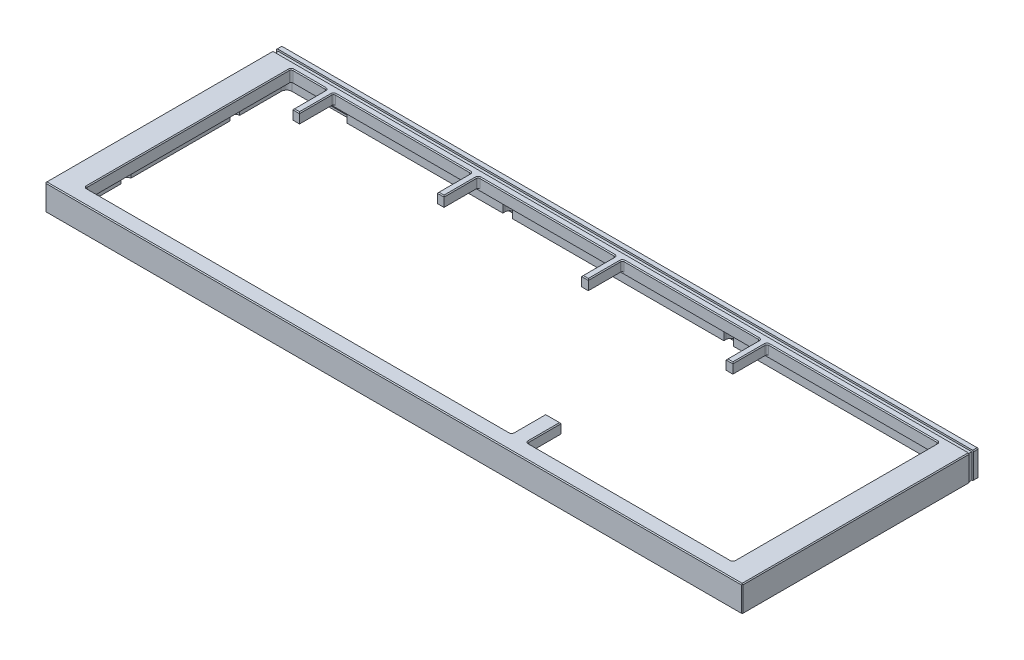
SolidWorks part; units mm, degrees
material "6061-T6 (SS)"
ref_plane "Front Plane" through (0, 0, 0) normal (0, 0, 1) x (1, 0, 0)
ref_plane "Top Plane" through (0, 0, 0) normal (0, 1, 0) x (1, 0, 0)
ref_plane "Right Plane" through (0, 0, 0) normal (1, 0, 0) x (0, 0, -1)
sketch "Sketch1" plane through (0, 0, 0) normal (0, 1, 0) x (1, 0, 0)
  line L1 (0, 0) -> (390.74, 0)
  line L2 (0, 0) -> (0, 132.7)
  line L3 (0, 132.7) -> (390.74, 132.7)
  line L4 (390.74, 0) -> (390.74, 132.7)
  line L5 (13.92, 124) -> (376.82, 124)
  line L6 (13.92, 124) -> (13.92, 8.7)
  line L7 (13.92, 8.7) -> (376.82, 8.7)
  line L8 (376.82, 124) -> (376.82, 8.7)
  point P9 (195.37, 124)
  point P10 (195.37, 132.7)
  point P11 (13.92, 66.35)
  point P12 (0, 66.35)
  dimension "D1" = 362.9
  dimension "D2" = 115.3
  dimension "D3" = 8.7
  dimension "D4" = 13.92
extrude "Main Body" add sketch "Sketch1" along normal blind 14.8
sketch "Sketch2" plane through (0, 0, 0) normal (0, -1, 0) x (1, 0, 0)
  line L0 (390.74, -132.7) -> (0, -132.7) construction
  line L1 (388.74, -130.7) -> (2, -130.7)
  line L2 (388.74, -130.7) -> (388.74, -2)
  line L3 (388.74, -2) -> (2, -2)
  line L4 (2, -130.7) -> (2, -2)
  line L5 (390.74, 0) -> (390.74, -132.7) construction
  point P4 (195.37, -130.7)
  point P7 (195.37, -132.7)
  point P8 (388.74, -66.35)
  point P11 (390.74, -66.35)
  dimension "D1" = 2
  dimension "D2" = 2
extrude "Alignment Guide" cut sketch "Sketch2" against normal blind 2 contours L2 L1 L4 L3
sketch "Sketch3" plane through (0, 14.8, 0) normal (0, 1, 0) x (1, 0, 0)
  line L0 (13.92, 8.7) -> (376.82, 8.7) construction
  line L1 (252.82, 27.8) -> (261.52, 27.8)
  line L2 (252.82, 27.8) -> (252.82, 8.7)
  line L3 (252.82, 8.7) -> (261.52, 8.7)
  line L4 (261.52, 27.8) -> (261.52, 8.7)
  line L5 (376.82, 8.7) -> (376.82, 124) construction
  line L6 (376.82, 124) -> (13.92, 124) construction
  line L7 (33.92, 124) -> (37.72, 124)
  line L8 (33.92, 124) -> (33.92, 104.9)
  line L9 (33.92, 104.9) -> (37.72, 104.9)
  line L10 (37.72, 124) -> (37.72, 104.9)
  line L11 (13.92, 124) -> (13.92, 8.7) construction
  line L12 (114.92, 124) -> (118.72, 124)
  line L13 (114.92, 124) -> (114.92, 104.9)
  line L14 (114.92, 104.9) -> (118.72, 104.9)
  line L15 (118.72, 124) -> (118.72, 104.9)
  line L16 (195.82, 124) -> (199.62, 124)
  line L17 (195.82, 124) -> (195.82, 104.9)
  line L18 (195.82, 104.9) -> (199.62, 104.9)
  line L19 (199.62, 124) -> (199.62, 104.9)
  line L20 (276.82, 124) -> (280.62, 124)
  line L21 (276.82, 124) -> (276.82, 104.9)
  line L22 (276.82, 104.9) -> (280.62, 104.9)
  line L23 (280.62, 124) -> (280.62, 104.9)
  point P8 (257.17, 8.7)
  dimension "D1" = 115.3
  dimension "D2" = 124
  dimension "D3" = 19.1
  dimension "D4" = 3.8
  dimension "D5" = 19.1
  dimension "D6" = 77.2
  dimension "D7" = 77.1
  dimension "D8" = 77.2
  dimension "D9" = 20
extrude "Blockers" add sketch "Sketch3" against normal blind 5.5
fillet "Fillet5" radius 1 14 edges at (280.62, 12.05, -124) (276.82, 12.05, -124) (195.82, 12.05, -124) (199.62, 12.05, -124) (118.72, 12.05, -124) (114.92, 12.05, -124) (33.92, 12.05, -124) (37.72, 12.05, -124) (13.92, 8.4, -124) (13.92, 8.4, -8.7) (252.82, 12.05, -8.7) (261.52, 12.05, -8.7) (376.82, 8.4, -8.7) (376.82, 8.4, -124)
sketch "Sketch4" plane through (0, 2, 0) normal (0, -1, 0) x (1, 0, 0)
  line L0 (0, 0) -> (390.74, 0) construction
  line L1 (381.27, -125.9) -> (9.47, -125.9)
  line L2 (381.27, -125.9) -> (381.27, -6.8)
  line L3 (381.27, -6.8) -> (9.47, -6.8)
  line L4 (9.47, -125.9) -> (9.47, -6.8)
  line L5 (390.74, 0) -> (390.74, -132.7) construction
  point P4 (195.37, -6.8)
  point P7 (195.37, 0)
  point P8 (381.27, -66.35)
  point P11 (390.74, -66.35)
  dimension "D1" = 119.1
  dimension "D2" = 371.8
extrude "PCB Cutout" cut sketch "Sketch4" against normal offset from surface (6.3 mm away) 6.5 up to face at (195.37, 14.8, -66.35)
fillet "Fillet4" radius 3 8 edges at (9.47, 5.15, -6.8) (9.47, 5.15, -125.9) (381.27, 5.15, -125.9) (381.27, 5.15, -6.8) (2, 1, -130.7) (2, 1, -2) (388.74, 1, -2) (388.74, 1, -130.7)
sketch "Sketch6" plane through (0, 2, 0) normal (0, -1, 0) x (1, 0, 0)
  line L0 (381.27, -9.8) -> (381.27, -122.9) construction
  line L1 (254.59, -127.1) -> (260.09, -127.1)
  line L2 (254.59, -127.1) -> (254.59, -125.9)
  line L3 (254.59, -125.9) -> (260.09, -125.9)
  line L4 (260.09, -127.1) -> (260.09, -125.9)
  line L5 (12.47, -125.9) -> (378.27, -125.9) construction
  line L11 (378.27, -6.8) -> (12.47, -6.8) construction
  line L16 (260.09, -6.8) -> (254.59, -6.8)
  line L17 (260.09, -6.8) -> (260.09, -4.8)
  line L18 (260.09, -4.8) -> (254.59, -4.8)
  line L19 (254.59, -6.8) -> (254.59, -4.8)
  line L21 (0, 0) -> (390.74, 0) construction
  line L24 (390.74, -66.35) -> (195.37, -66.35) construction
  line L25 (390.74, 0) -> (390.74, -132.7) construction
  line L26 (328.6755, -66.35) -> (328.6755, -130.7) construction
  line L27 (385.74, -130.7) -> (5, -130.7) construction
  line L28 (328.6755, -66.35) -> (328.6755, -8.7) construction
  line L29 (375.82, -8.7) -> (14.92, -8.7) construction
  line L55 (390.74, -132.7) -> (0, -132.7) construction
  line L56 (195.37, -132.7) -> (195.37, 0) construction
  line L57 (136.15, -6.8) -> (136.15, -4.8)
  line L58 (130.65, -4.8) -> (136.15, -4.8)
  line L59 (130.65, -6.8) -> (130.65, -4.8)
  line L60 (130.65, -6.8) -> (136.15, -6.8)
  line L61 (130.65, -127.1) -> (130.65, -125.9)
  line L62 (136.15, -125.9) -> (130.65, -125.9)
  line L63 (136.15, -127.1) -> (136.15, -125.9)
  line L64 (136.15, -127.1) -> (130.65, -127.1)
  circle A0 centre (381.07, -96.85) radius 2.75
  circle A1 centre (381.07, -35.85) radius 2.75
  circle A2 centre (257.34, -4.8) radius 2.75
  circle A3 centre (257.34, -127.1) radius 2.75
  circle A8 centre (133.4, -4.8) radius 2.75
  circle A9 centre (9.67, -35.85) radius 2.75
  circle A10 centre (9.67, -96.85) radius 2.75
  circle A11 centre (133.4, -127.1) radius 2.75
  point P25 (195.37, -66.35)
  point P32 (257.34, -125.9)
  point P33 (257.34, -6.8)
  line M17 (12.47, -6.8) -> (378.27, -6.8)
  line M18 (381.27, -9.8) -> (381.27, -122.9)
  line M19 (378.27, -125.9) -> (12.47, -125.9)
  line M20 (9.47, -122.9) -> (9.47, -9.8)
  dimension "D4" = 5.5
  dimension "D5" = 133.4
  dimension "D1" = 30.5
  dimension "D2" = 4.8
  dimension "D3" = 30.5
  dimension "D6" = 0.2
  dimension "D7" = 5.6
extrude "PlateTabs" cut sketch "Sketch6" against normal up to surface (6.3 mm away) contours A0 M18 | A1 M18 | A2 L19 M17 | L16 A2 L18 | A2 L17 M17 | L18 A2 | L1 A3 | L1 A3 L3 | A3 L2 M19 | A11 L64 | A11 L64 L62 | A10 M20 | A9 M20 | A8 L58 | A8 L60 L58 | A3 L4 M19 | A8 L59 M17 | L57 A8 M17 | A11 L63 M19 | L61 A11 M19 | A11 | L59 L58 L57 L60 | A3 region at (257.34, 2, -126.5102) region at (136.0681, 2, -126.1969) region at (257.34, 2, -128.2671) region at (254.6719, 2, -126.1969) region at (260.0081, 2, -126.1969) region at (133.4, 2, -126.5102) region at (133.4, 2, -128.2671) region at (130.7319, 2, -126.1969) region at (135.9001, 2, -6.317) region at (259.8401, 2, -6.317) region at (257.34, 2, -5.7445) region at (257.34, 2, -3.6329) region at (254.8399, 2, -6.317) region at (133.4, 2, -5.7445) region at (133.4, 2, -3.6329) region at (130.8999, 2, -6.317) region at (382.3459, 2, -96.85) region at (382.3459, 2, -35.85) region at (8.3941, 2, -96.85) region at (8.3941, 2, -35.85) up to face at (195.37, 8.3, -66.35)
sketch "Sketch9" plane through (0, 0, -132.7) normal (0, 0, -1) x (-1, 0, 0)
  line L1 (-40.9, 2.4) -> (-30.9, 2.4)
  line L2 (-40.9, 2.4) -> (-40.9, 7.4)
  line L3 (-40.9, 7.4) -> (-30.9, 7.4)
  line L4 (-30.9, 2.4) -> (-30.9, 7.4)
  line L7 (0, 14.8) -> (0, 0) construction
  line L8 (-390.74, 0) -> (0, 0) construction
  point P4 (-30.9, 4.9)
  point P6 (-35.9, 7.4)
  dimension "D1" = 4.9
  dimension "D2" = 5
  dimension "D3" = 10
  dimension "D4" = 35.9
extrude "USB Cutout" cut sketch "Sketch9" against normal up to surface (8.7 mm away) up to face at (164.89, 11.95, -124)
sketch "Sketch10" plane through (0, 0, -132.7) normal (0, 0, -1) x (-1, 0, 0)
  line L0 (-30.9, 7.4) -> (-40.9, 7.4) construction
  line L1 (-42.9, 9.4) -> (-28.9, 9.4)
  line L2 (-42.9, 9.4) -> (-42.9, 0.4)
  line L3 (-42.9, 0.4) -> (-28.9, 0.4)
  line L4 (-28.9, 9.4) -> (-28.9, 0.4)
  line L5 (-40.9, 7.4) -> (-40.9, 2.4) construction
  point P4 (-35.9, 9.4)
  point P7 (-35.9, 7.4)
  point P10 (-40.9, 4.9)
  point P11 (-42.9, 4.9)
  dimension "D1" = 2
  dimension "D2" = 2
extrude "USB Outline" cut sketch "Sketch10" against normal blind 1
sketch "Sketch11" plane through (0, 0, -125.9) normal (0, 0, 1) x (1, 0, 0)
  line L1 (43.4, 2) -> (28.4, 2)
  line L2 (43.4, 2) -> (43.4, 7.4)
  line L3 (43.4, 7.4) -> (28.4, 7.4)
  line L4 (28.4, 2) -> (28.4, 7.4)
  line L5 (30.9, 7.4) -> (40.9, 7.4) construction
  line L6 (40.9, 2.4) -> (30.9, 2.4) construction
  line L7 (12.47, 2) -> (130.65, 2) construction
  point P8 (35.9, 2)
  point P11 (35.9, 2.4)
  dimension "D1" = 15
extrude "PCB Clearance" cut sketch "Sketch11" against normal blind 3.9
fillet "Fillet6" radius 1.5 8 edges at (40.9, 7.4, -130.75) (30.9, 7.4, -130.75) (40.9, 2.4, -130.75) (42.9, 0.4, -132.2) (42.9, 9.4, -132.2) (28.9, 9.4, -132.2) (30.9, 2.4, -130.75) (28.9, 0.4, -132.2)
fillet "Fillet7" radius 2.5 2 edges at (28.4, 4.7, -129.8) (43.4, 4.7, -129.8)
sketch "Sketch12" plane through (0, 8.3, 0) normal (0, -1, 0) x (1, 0, 0)
  line L0 (195.37, -132.7) -> (195.37, 0) construction
  line L1 (390.74, -132.7) -> (0, -132.7) construction
  line L2 (14.92, -124) -> (375.82, -124) construction
  line L3 (0, 0) -> (390.74, 0) construction
  line L4 (390.74, 0) -> (390.74, -132.7) construction
  line L8 (376.82, -123) -> (376.82, -9.7) construction
  line L9 (375.82, -8.7) -> (14.92, -8.7) construction
  arc A0 (381.27, -38.5927) -> (381.27, -33.1073) centre (381.07, -35.85) ccw construction
  arc A1 (381.27, -99.5927) -> (381.27, -94.1073) centre (381.07, -96.85) ccw construction
  point P0 (257.34, -127.1)
  point P1 (381.42, -96.85)
  point P2 (381.42, -35.85)
  point P3 (257.34, -4.8)
  point P8 (133.4, -4.8)
  point P10 (9.32, -35.85)
  point P14 (9.32, -96.85)
  point P16 (133.4, -127.1)
  point P34 (383.82, -35.85)
  point P39 (383.82, -96.85)
  dimension "D1" = 3.1
  dimension "D2" = 3.9
  dimension "D3" = 4.6
  dimension "D4" = 133.4
sketch "Sketch14" plane through (0, 2, 0) normal (0, -1, 0) x (1, 0, 0)
  line L0 (195.37, -132.7) -> (195.37, 0) construction
  line L1 (390.74, -132.7) -> (0, -132.7) construction
  line L2 (0, 0) -> (390.74, 0) construction
  line L5 (195.37, -66.35) -> (390.74, -66.35) construction
  line L6 (390.74, 0) -> (390.74, -132.7) construction
  line L7 (388.74, -127.7) -> (388.74, -5) construction
  line L8 (385.74, -130.7) -> (5, -130.7) construction
  line L9 (385.74, -2) -> (5, -2) construction
  point P8 (385.04, -111.35)
  point P9 (385.04, -66.35)
  point P10 (385.04, -21.35)
  point P11 (280.74, -4.4)
  point P20 (280.74, -128.3)
  point P22 (110, -4.4)
  point P28 (110, -128.3)
  point P29 (5.7, -21.35)
  point P30 (5.7, -66.35)
  point P31 (5.7, -111.35)
  dimension "D1" = 2.4
  dimension "D2" = 2.4
  dimension "D3" = 110
  dimension "D4" = 45
  dimension "D5" = 45
  dimension "D6" = 3.7
chamfer "Chamfer1" distance 0.5 42 edges at (14.2129, 14.8, -8.9929) (133.37, 14.8, -8.7) (252.5271, 14.8, -8.9929) (252.82, 14.8, -18.75) (257.17, 14.8, -27.8) (261.52, 14.8, -18.75) (261.8129, 14.8, -8.9929) (319.17, 14.8, -8.7) (376.5271, 14.8, -8.9929) (376.82, 14.8, -66.35) (376.5271, 14.8, -123.7071) (328.72, 14.8, -124) (280.9129, 14.8, -123.7071) (280.62, 14.8, -113.95) (278.72, 14.8, -104.9) (276.82, 14.8, -113.95) (276.5271, 14.8, -123.7071) (238.22, 14.8, -124) (199.9129, 14.8, -123.7071) (199.62, 14.8, -113.95) (197.72, 14.8, -104.9) (195.82, 14.8, -113.95) (195.5271, 14.8, -123.7071) (157.27, 14.8, -124) (119.0129, 14.8, -123.7071) (118.72, 14.8, -113.95) (116.82, 14.8, -104.9) (114.92, 14.8, -113.95) (114.6271, 14.8, -123.7071) (76.32, 14.8, -124) (38.0129, 14.8, -123.7071) (37.72, 14.8, -113.95) (35.82, 14.8, -104.9) (33.92, 14.8, -113.95) (33.6271, 14.8, -123.7071) (23.92, 14.8, -124) (14.2129, 14.8, -123.7071) (13.92, 14.8, -66.35) (195.37, 14.8, -132.7) (390.74, 14.8, -66.35) (195.37, 14.8, 0) (0, 14.8, -66.35)
chamfer "Chamfer2" distance 0.5 8 edges at (0, 7.15, -132.7) (195.37, 0, -132.7) (390.74, 7.15, -132.7) (390.74, 0, -66.35) (390.74, 7.15, 0) (0, 7.15, 0) (195.37, 0, 0) (0, 0, -66.35)
sketch "Sketch27" plane through (0, 14.8, 0) normal (0, 1, 0) x (1, 0, 0)
  line L0 (0, 0.5) -> (0, 132.2) construction
  line L1 (0, 129.7) -> (390.74, 129.7)
  line L2 (0, 129.7) -> (0, 127.2)
  line L3 (0, 127.2) -> (390.74, 127.2)
  line L4 (390.74, 129.7) -> (390.74, 127.2)
  line L5 (390.74, 132.2) -> (390.74, 0.5) construction
  line L8 (0.5, 132.7) -> (390.24, 132.7) construction
  dimension "D1" = 2.5
  dimension "D2" = 3
extrude "Cut-Extrude11" cut sketch "Sketch27" against normal blind 1
sketch "Sketch28" plane through (0, 13.8, 0) normal (0, 1, 0) x (1, 0, 0)
  line L1 (0, 129.7) -> (1, 129.7)
  line L2 (0, 129.7) -> (0, 127.2)
  line L3 (0, 127.2) -> (1, 127.2)
  line L4 (1, 129.7) -> (1, 127.2)
  line L5 (389.74, 129.7) -> (390.74, 129.7)
  line L6 (389.74, 129.7) -> (389.74, 127.2)
  line L7 (389.74, 127.2) -> (390.74, 127.2)
  line L8 (390.74, 129.7) -> (390.74, 127.2)
  line L9 (390.74, 129.7) -> (0, 129.7) construction
  line L10 (0, 127.2) -> (390.74, 127.2) construction
  dimension "D1" = 1
  dimension "D2" = 1
extrude "Cut-Extrude12" cut sketch "Sketch28" against normal through all
sketch "Sketch21" [suppressed] plane through (0, 14.8, 0) normal (0, 1, 0) x (1, 0, 0)
  line L0 (0.5, 132.7) -> (390.24, 132.7) construction
  line L1 (382.53, 132.7) -> (385.03, 132.7)
  line L2 (382.53, 132.7) -> (382.53, 72.7)
  line L3 (382.53, 72.7) -> (385.03, 72.7)
  line L4 (385.03, 132.7) -> (385.03, 72.7)
  line L5 (390.74, 132.2) -> (390.74, 129.7) construction
  line L6 (390.74, 129.1) -> (294.74, 129.1)
  line L7 (390.74, 129.1) -> (390.74, 127.6)
  line L8 (390.74, 127.6) -> (294.74, 127.6)
  line L9 (294.74, 129.1) -> (294.74, 127.6)
  line L10 (362.9081, 132.2) -> (362.9081, 124.5) construction
  line L11 (390.24, 132.2) -> (0.5, 132.2) construction
  line L12 (281.62, 124.5) -> (375.82, 124.5) construction
  line L13 (365.5702, 129.1) -> (365.5702, 127.6) construction
  line L14 (377.32, 119.5259) -> (390.24, 119.5259) construction
  line L15 (377.32, 123) -> (377.32, 9.7) construction
  line L16 (390.24, 0.5) -> (390.24, 127.2) construction
  line L17 (382.53, 116.0504) -> (385.03, 116.0504) construction
  point P28 (383.78, 116.0504)
  point P29 (383.78, 119.5259)
  point P30 (365.5702, 128.35)
  point P31 (362.9081, 128.35)
  dimension "D1" = 2.5
  dimension "D2" = 1.5
  dimension "D3" = 60
  dimension "D4" = 96
extrude "Cut-Extrude5" [suppressed] cut sketch "Sketch21" against normal blind 1 contours L4 L3 L2 L1 | L8 L9 L6 L7
sketch "Sketch23" [suppressed] plane through (390.74, 0, 0) normal (1, 0, 0) x (0, 0, -1)
  line L0 (129.1, 13.8) -> (129.1, 14.3) construction
  line L1 (127.6, 13.8) -> (129.1, 13.8)
  line L2 (127.6, 13.8) -> (127.6, 0)
  line L3 (127.6, 0) -> (129.1, 0)
  line L4 (129.1, 13.8) -> (129.1, 0)
extrude "Cut-Extrude6" [suppressed] cut sketch "Sketch23" against normal blind 1
sketch "Sketch20" plane through (0, 14.8, 0) normal (0, 1, 0) x (1, 0, 0)
  line L0 (0, 0.5) -> (0, 127.2) construction
  line L1 (0, 129.1) -> (390.74, 129.1)
  line L2 (0, 129.1) -> (0, 127.6)
  line L3 (0, 127.6) -> (390.74, 127.6)
  line L4 (390.74, 129.1) -> (390.74, 127.6)
  line L5 (390.74, 132.2) -> (390.74, 129.7) construction
  line L6 (0.5, 132.7) -> (390.24, 132.7) construction
  line L7 (381.7523, 132.7) -> (384.2523, 132.7)
  line L8 (381.7523, 132.7) -> (381.7523, 0)
  line L9 (381.7523, 0) -> (384.2523, 0)
  line L10 (384.2523, 132.7) -> (384.2523, 0)
  line L11 (390.24, 0) -> (0.5, 0) construction
  line L12 (376.82, 111.1489) -> (390.74, 111.1489) construction
  line L13 (376.82, 9.7) -> (376.82, 123) construction
  line L14 (381.7523, 114.604) -> (384.2523, 114.604) construction
  line L15 (369.2566, 124.5) -> (369.2566, 132.2) construction
  line L16 (281.62, 124.5) -> (375.82, 124.5) construction
  line L17 (390.24, 132.2) -> (0.5, 132.2) construction
  line L18 (371.0168, 127.6) -> (371.0168, 129.1) construction
  point P30 (371.0168, 128.35)
  point P31 (369.2566, 128.35)
  dimension "D1" = 2.5
  dimension "D2" = 1.5
extrude "Cut-Extrude4" [suppressed] cut sketch "Sketch20" against normal blind 1
sketch "Sketch19" plane through (0, 14.8, 0) normal (0, 1, 0) x (1, 0, 0)
  line L0 (0.5, 132.7) -> (390.24, 132.7) construction
  line L1 (5.46, 132.7) -> (8.46, 132.7)
  line L2 (5.46, 132.7) -> (5.46, 0)
  line L3 (5.46, 0) -> (8.46, 0)
  line L4 (8.46, 132.7) -> (8.46, 0)
  line L7 (382.28, 132.7) -> (385.28, 132.7)
  line L8 (382.28, 132.7) -> (382.28, 0)
  line L9 (382.28, 0) -> (385.28, 0)
  line L10 (385.28, 132.7) -> (385.28, 0)
  line L11 (390.24, 0) -> (0.5, 0) construction
  line L12 (377.32, 110.209) -> (390.24, 110.209) construction
  line L13 (377.32, 123) -> (377.32, 9.7) construction
  line L14 (390.24, 0.5) -> (390.24, 127.2) construction
  line L15 (382.28, 106.8719) -> (385.28, 106.8719) construction
  line L16 (0.5, 106.8719) -> (13.42, 106.8719) construction
  line L17 (0.5, 132.2) -> (0.5, 129.7) construction
  line L18 (13.42, 9.7) -> (13.42, 123) construction
  line L19 (5.46, 102.7297) -> (8.46, 102.7297) construction
  point P12 (383.78, 106.8719)
  point P14 (383.78, 110.209)
  point P30 (6.96, 102.7297)
  point P31 (6.96, 106.8719)
  dimension "D1" = 3
  dimension "D2" = 3
extrude "Cut-Extrude3" [suppressed] cut sketch "Sketch19" against normal blind 1
sketch "Sketch17" plane through (0, 14.8, 0) normal (0, 1, 0) x (1, 0, 0)
  line L0 (390.24, 0.5) -> (390.24, 127.2) construction
  line L1 (5.71, 129.6) -> (385.03, 129.6)
  line L2 (5.71, 129.6) -> (5.71, -1.9)
  line L3 (5.71, -1.9) -> (385.03, -1.9)
  line L4 (385.03, 129.6) -> (385.03, -1.9)
  line L5 (8.21, 127.1) -> (382.53, 127.1)
  line L6 (8.21, 127.1) -> (8.21, 0.6)
  line L7 (8.21, 0.6) -> (382.53, 0.6)
  line L8 (382.53, 127.1) -> (382.53, 0.6)
  line L9 (390.24, 132.2) -> (0.5, 132.2) construction
  line L10 (21.2533, 132.2) -> (21.2533, 124.5) construction
  line L11 (14.92, 124.5) -> (32.92, 124.5) construction
  line L12 (25.2757, 129.6) -> (25.2757, 127.1) construction
  line L13 (0.5, 116.1326) -> (13.42, 116.1326) construction
  line L14 (0.5, 132.2) -> (0.5, 129.7) construction
  line L15 (13.42, 9.7) -> (13.42, 123) construction
  line L16 (5.71, 120.1548) -> (8.21, 120.1548) construction
  point P8 (382.53, 63.85)
  point P9 (385.03, 63.85)
  point P12 (390.24, 63.85)
  point P13 (195.37, 129.6)
  point P14 (195.37, 127.1)
  point P17 (195.37, 132.2)
  point P24 (25.2757, 128.35)
  point P25 (21.2533, 128.35)
  point P34 (6.96, 116.1326)
  point P35 (6.96, 120.1548)
  dimension "D1" = 2.5
  dimension "D2" = 2.5
extrude "Cut-Extrude1" [suppressed] cut sketch "Sketch17" against normal blind 1
hole_wizard "M3x0.5 Tapped Hole1" positions "3DSketch1" profile "Sketch29" tap size "M3x0.5" standard "ANSI Metric"
sketch3d "3DSketch1"
  point P0 (385.04, 2, -111.35)
  point P3 (385.04, 2, -21.35)
  point P6 (280.74, 2, -4.4)
  point P9 (110, 2, -4.4)
  point P12 (5.7, 2, -21.35)
  point P15 (5.7, 2, -66.35)
  point P18 (5.7, 2, -111.35)
  point P21 (110, 2, -128.3)
  point P24 (280.74, 2, -128.3)
  point P28 (385.04, 2, -66.35)
sketch "Sketch29" plane through (385.04, 2, -111.35) normal (1, 0, 0) x (0, 0, -1)
  line L0 (0, 0) -> (0, 4.7511)
  line L1 (0, 4.7511) -> (1.25, 4)
  line L2 (1.25, 4) -> (1.25, 0)
  line L5 (1.25, 0) -> (0, 0)
  line L10 (0, 4.7511) -> (-1.25, 4) construction
  line L11 (0, -6.35) -> (0, 107.95) construction
  dimension "Tap Drill Dia." = 2.5
  dimension "Tap Drill Depth" = 4
  dimension "Drill Angle" = 118
cosmetic thread "Hole Thread1" parameters "D1"=4, "D2"=3
cosmetic thread "Hole Thread2" parameters "D1"=4, "D2"=3
cosmetic thread "Hole Thread3" parameters "D1"=4, "D2"=3
cosmetic thread "Hole Thread4" parameters "D1"=4, "D2"=3
cosmetic thread "Hole Thread5" parameters "D1"=4, "D2"=3
cosmetic thread "Hole Thread6" parameters "D1"=4, "D2"=3
cosmetic thread "Hole Thread7" parameters "D1"=4, "D2"=3
cosmetic thread "Hole Thread8" parameters "D1"=4, "D2"=3
cosmetic thread "Hole Thread9" parameters "D1"=4, "D2"=3
cosmetic thread "Hole Thread18" parameters "D1"=4, "D2"=3
hole_wizard "M2x0.4 Tapped Hole4" positions "3DSketch3" profile "Sketch31" tap size "M2x0.4" standard "ANSI Metric"
sketch3d "3DSketch3"
  line L0 (381.07, 8.3, -96.85) -> (381.07, 2, -96.85) construction
  line L1 (381.07, 8.3, -35.85) -> (381.07, 2, -35.85) construction
  line L2 (9.67, 8.3, -35.85) -> (9.67, 2, -35.85) construction
  line L3 (9.67, 8.3, -96.85) -> (9.67, 2, -96.85) construction
  point P0 (381.07, 8.3, -96.85)
  point P5 (381.07, 8.3, -35.85)
  point P9 (257.34, 8.3, -4.8)
  point P12 (133.4, 8.3, -4.8)
  point P15 (9.67, 8.3, -35.85)
  point P19 (9.67, 8.3, -96.85)
  point P23 (133.4, 8.3, -127.1)
  point P26 (257.34, 8.3, -127.1)
sketch "Sketch31" plane through (381.07, 8.3, -96.85) normal (1, 0, 0) x (0, 0, -1)
  line L0 (0, 0) -> (0, 4.4807)
  line L1 (0, 4.4807) -> (0.8, 4)
  line L2 (0.8, 4) -> (0.8, 0)
  line L5 (0.8, 0) -> (0, 0)
  line L10 (0, 4.4807) -> (-0.8, 4) construction
  line L11 (0, -6.35) -> (0, 107.95) construction
  dimension "Tap Drill Dia." = 1.6
  dimension "Tap Drill Depth" = 4
  dimension "Drill Angle" = 118
cosmetic thread "Hole Thread19" parameters "D1"=4, "D2"=2
cosmetic thread "Hole Thread20" parameters "D1"=4, "D2"=2
cosmetic thread "Hole Thread21" parameters "D1"=4, "D2"=2
cosmetic thread "Hole Thread22" parameters "D1"=4, "D2"=2
cosmetic thread "Hole Thread23" parameters "D1"=4, "D2"=2
cosmetic thread "Hole Thread24" parameters "D1"=4, "D2"=2
cosmetic thread "Hole Thread25" parameters "D1"=4, "D2"=2
cosmetic thread "Hole Thread26" parameters "D1"=4, "D2"=2
